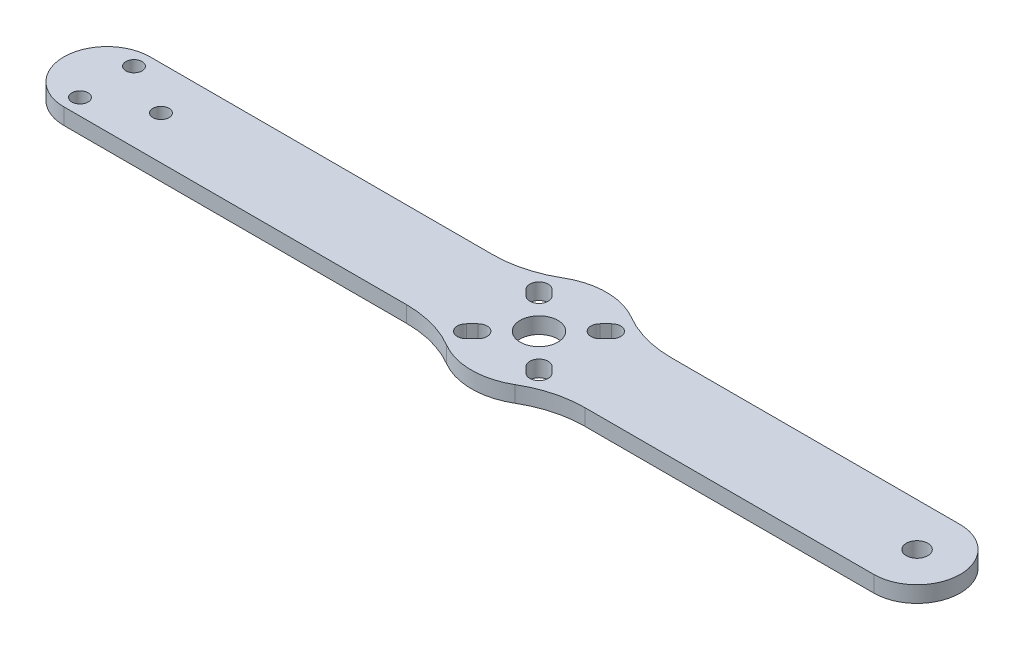
SolidWorks part; units mm, degrees
other "标注1"
sketch "草图10" plane through (158, 3, -12.5) normal (0.0162, 0.9997, -0.0168) x (0.5389, -0.0229, -0.8421)
other "标注2"
sketch "草图11" plane through (158, 3, -12.5) normal (0.0162, 0.9997, -0.0168) x (0.5389, -0.0229, -0.8421)
material "Thornel Mat VMA"
ref_plane "前视基准面" through (0, 0, 0) normal (0, 0, 1) x (1, 0, 0)
ref_plane "上视基准面" through (0, 0, 0) normal (0, 1, 0) x (1, 0, 0)
ref_plane "右视基准面" through (0, 0, 0) normal (1, 0, 0) x (0, 0, -1)
sketch "草图1" plane through (0, 0, 0) normal (0, 1, 0) x (1, 0, 0)
  line L0 (0, 0) -> (150, 0) construction
  line L1 (0, 8) -> (150, 8)
  line L2 (0, -8) -> (150, -8)
  arc A0 (0, 8) -> (0, -8) centre (0, 0) ccw
  arc A1 (150, -8) -> (150, 8) centre (150, 0) ccw
  point P3 (75, 0)
  dimension "D1" = 8
  dimension "D2" = 150
extrude "凸台-拉伸1" add sketch "草图1" along normal blind 3
sketch "草图8" plane through (0, 3, 0) normal (0, 1, 0) x (1, 0, 0)
  circle A0 centre (80, 0) radius 12.5
  dimension "D1" = 25
  dimension "D3" = 80
  dimension "D2" = 0
extrude "凸台-拉伸2" add sketch "草图8" against normal blind 3
sketch "草图2" plane through (0, 3, 0) normal (0, 1, 0) x (1, 0, 0)
  line L0 (80, 0) -> (85.6569, 5.6569) construction
  line L1 (150, 8) -> (89.6047, 8) construction
  line L2 (85.6569, 5.6569) -> (86.7175, 6.7175) construction
  line L5 (84.4562, 6.8575) -> (85.5169, 7.9181)
  line L6 (86.8575, 4.4562) -> (87.9181, 5.5169)
  line L7 (84.4562, -6.8575) -> (85.5169, -7.9181)
  line L8 (86.8575, -4.4562) -> (87.9181, -5.5169)
  line L9 (85.6569, -5.6569) -> (86.7175, -6.7175) construction
  line L10 (73.1425, -4.4562) -> (72.0819, -5.5169)
  line L11 (75.5438, -6.8575) -> (74.4831, -7.9181)
  line L12 (74.3431, -5.6569) -> (73.2825, -6.7175) construction
  line L13 (75.5438, 6.8575) -> (74.4831, 7.9181)
  line L14 (73.1425, 4.4562) -> (72.0819, 5.5169)
  line L15 (74.3431, 5.6569) -> (73.2825, 6.7175) construction
  circle A0 centre (80, 0) radius 3.5
  arc A7 (84.4562, 6.8575) -> (86.8575, 4.4562) centre (85.6569, 5.6569) ccw
  arc A8 (87.9181, 5.5169) -> (85.5169, 7.9181) centre (86.7175, 6.7175) ccw
  arc A9 (86.8575, -4.4562) -> (84.4562, -6.8575) centre (85.6569, -5.6569) ccw
  arc A10 (85.5169, -7.9181) -> (87.9181, -5.5169) centre (86.7175, -6.7175) ccw
  arc A11 (75.5438, -6.8575) -> (73.1425, -4.4562) centre (74.3431, -5.6569) ccw
  arc A12 (72.0819, -5.5169) -> (74.4831, -7.9181) centre (73.2825, -6.7175) ccw
  arc A13 (73.1425, 4.4562) -> (75.5438, 6.8575) centre (74.3431, 5.6569) ccw
  arc A14 (74.4831, 7.9181) -> (72.0819, 5.5169) centre (73.2825, 6.7175) ccw
  point P3 (86.1872, 6.1872)
  point P16 (80, 0)
  point P17 (86.1872, -6.1872)
  point P24 (73.8128, -6.1872)
  point P31 (73.8128, 6.1872)
  point P37 (80, 0)
  dimension "D2" = 8
  dimension "D3" = 45
  dimension "D4" = 9.5
  dimension "D6" = 7
  dimension "D1" = 80
  dimension "D7" = 0
  dimension "D8" = 0
  dimension "D5" = 4
extrude "切除-拉伸1" cut sketch "草图2" against normal through all
sketch "草图5" plane through (0, 3, 0) normal (0, 1, 0) x (1, 0, 0)
  circle A0 centre (10, 0) radius 1.5
  circle A1 centre (0, 5) radius 1.5
  circle A2 centre (0, -5) radius 1.5
  dimension "D1" = 3
  dimension "D2" = 3
  dimension "D3" = 3
  dimension "D4" = 5
  dimension "D5" = 5
  dimension "D6" = 10
extrude "切除-拉伸2" cut sketch "草图5" against normal through all
fillet "圆角3" radius 20 4 edges at (70.3953, 1.5, 8) (89.6047, 1.5, 8) (89.6047, 1.5, -8) (70.3953, 1.5, -8)
sketch "草图9" plane through (0, 3, 0) normal (0, 1, 0) x (1, 0, 0)
  circle A0 centre (150, 0) radius 2
  dimension "D1" = 4
extrude "切除-拉伸3" cut sketch "草图9" against normal through all
